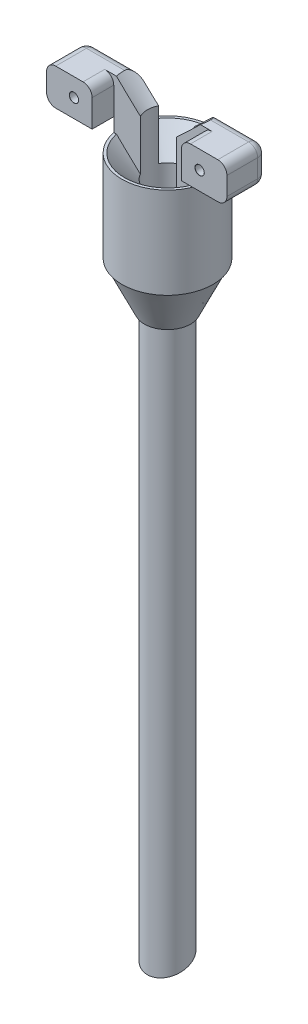
SolidWorks part; units mm, degrees
ref_plane "Front Plane" through (0, 0, 0) normal (0, 0, 1) x (1, 0, 0)
ref_plane "Top Plane" through (0, 0, 0) normal (0, 1, 0) x (1, 0, 0)
ref_plane "Right Plane" through (0, 0, 0) normal (1, 0, 0) x (0, 0, -1)
sketch "Sketch1" plane through (0, 0, 0) normal (0, 1, 0) x (1, 0, 0)
  circle A0 centre (0, 0) radius 1.7
  circle A1 centre (0, 0) radius 4.425
  dimension "D1" = 3.4
  dimension "D2" = 8.85
extrude "Boss-Extrude1" add sketch "Sketch1" along normal blind 130
chamfer "Chamfer1" distance 5 angle 60 1 edges at (0, 130, 1.7) first distance on face at (0, 130, 4.425)
ref_plane "Plane1" through (0, 126.0596, 0) normal (0, 1, 0) x (1, 0, 0)
sketch "Sketch2" plane through (0, 126.0596, 0) normal (0, 1, 0) x (1, 0, 0)
  circle A0 centre (0, 0) radius 10
  circle A1 centre (0, 0) radius 4.425
  dimension "D1" = 20
extrude "Boss-Extrude2" add sketch "Sketch2" along normal blind 20 separate body
ref_point "Point1"
ref_axis "Axis1" through (0, 126.0596, 0) along (0, -1, 0)
sketch "Sketch5" plane through (0, 126.0596, 0) normal (0, -1, 0) x (1, 0, 0)
  line L0 (0, 0) -> (2.7, 3.5058)
  circle A0 centre (0, 0) radius 4.425 construction
ref_plane "Plane2" through (2.7, 126.0596, 3.5058) normal (0.6102, 0, 0.7923) x (0.7923, 0, -0.6102)
sketch "Sketch10" plane through (0, 146.0596, 0) normal (0, 1, 0) x (1, 0, 0)
  line L0 (-3.9472, -2) -> (-9.798, -2)
  line L1 (-3.9472, 2) -> (-9.798, 2)
  line L2 (3.9472, 2) -> (9.798, 2)
  line L3 (3.9472, -2) -> (9.798, -2)
  line L4 (9.798, 2) -> (9.798, -2)
  line L5 (-9.798, 2) -> (-9.798, -2)
  line L6 (0, 10) -> (0, -10) construction
  circle A0 centre (0, 0) radius 4.425 construction
  circle A1 centre (0, 0) radius 10 construction
  circle A2 centre (0, 0) radius 4.425 construction
  arc A4 (3.9472, 2) -> (3.9472, -2) centre (0, 0) cw
  arc A5 (-3.9472, -2) -> (-3.9472, 2) centre (0, 0) cw
  dimension "D1" = 4
extrude "Boss-Extrude5" add sketch "Sketch10" along normal blind 11
sketch "Sketch11" plane through (9.798, 0, 0) normal (1, 0, 0) x (0, 0, -1)
  line L0 (-2, 146.0596) -> (2, 146.0596) construction
  line L1 (-2, 157.0596) -> (2, 157.0596)
  line L2 (-2, 157.0596) -> (-2, 149.0596)
  line L3 (-2, 149.0596) -> (2, 149.0596)
  line L4 (2, 157.0596) -> (2, 149.0596)
  line L5 (2, 157.0596) -> (2, 146.0596) construction
  dimension "D1" = 3
extrude "Boss-Extrude6" add sketch "Sketch11" along normal blind 10
sketch "Sketch13" plane through (0, 0, 2) normal (0, 0, 1) x (1, 0, 0)
  line L1 (9.798, 149.0596) -> (19.798, 149.0596)
  line L2 (9.798, 149.0596) -> (9.798, 157.0596)
  line L3 (9.798, 157.0596) -> (19.798, 157.0596)
  line L4 (19.798, 149.0596) -> (19.798, 157.0596)
extrude "Boss-Extrude7" add sketch "Sketch13" along normal blind 4.75
fillet "Fillet1" radius 2 3 edges at (9.798, 157.0596, 4.375) (19.798, 149.0596, 2.375) (19.798, 157.0596, 2.375)
ref_plane "Plane3" through (0, 0, 0) normal (1, 0, 0) x (0, 0, -1)
mirror "Mirror1" about plane through (0, 0, 0) normal (1, 0, 0) of "Fillet1", "Boss-Extrude6", "Boss-Extrude5", "Boss-Extrude7"
chamfer "Chamfer4" distance 5 angle 45 2 edges at (-4.425, 157.0596, 0) (4.425, 157.0596, 0)
chamfer "Chamfer2" distance 5 angle 45 2 edges at (0, 146.0596, 4.425) (0, 146.0596, -4.425)
sketch "Sketch7" plane through (0, 126.0596, 0) normal (0, -1, 0) x (1, 0, 0)
  circle A0 centre (0, 0) radius 4.425
  circle A1 centre (0, 0) radius 9.75
extrude "Boss-Extrude3" add sketch "Sketch7" along normal blind 10
chamfer "Chamfer3" distance 10 angle 25 1 edges at (0, 116.0596, -9.75) first distance on face at (0, 116.0596, -9.75)
sketch "Sketch8" plane through (0, 0, 0) normal (0, -1, 0) x (1, 0, 0)
  circle A0 centre (0, 0) radius 1.7
  circle A1 centre (0, 0) radius 4.425
  circle A4 centre (0, 0) radius 1.7 construction
  circle A5 centre (0, 0) radius 4.425 construction
extrude "Boss-Extrude4" add sketch "Sketch8" along normal blind 8
sketch "Sketch9" plane through (0, 0, 0) normal (1, 0, 0) x (0, 0, -1)
  line L0 (-4.425, -8) -> (4.425, -5)
  line L1 (4.425, -8) -> (4.425, 116.0596) construction
  line L2 (4.425, -5) -> (4.425, -8)
  line L3 (4.425, -8) -> (-4.425, -8)
  dimension "D1" = 3
extrude "Cut-Extrude1" cut sketch "Sketch9" against normal blind 8 and the other way blind 8
fillet "Fillet2" radius 2 10 edges at (13.798, 149.0596, -2) (19.2122, 149.6454, -2) (19.798, 153.0596, -2) (19.2122, 156.4738, -2) (-13.798, 149.0596, -2) (-19.2122, 149.6454, -2) (-19.798, 153.0596, -2) (-19.2122, 156.4738, -2) (13.5042, 157.0596, -2) (-13.5042, 157.0596, -2)
sketch "Sketch14" plane through (0, 0, 6.75) normal (0, 0, 1) x (1, 0, 0)
  line L0 (9.798, 149.0596) -> (17.798, 149.0596) construction
  line L1 (19.4941, 149.0596) -> (14.3598, 149.0596)
  line L2 (19.4941, 149.0596) -> (19.4941, 154.0596)
  line L3 (19.4941, 154.0596) -> (14.3598, 154.0596)
  line L4 (14.3598, 149.0596) -> (14.3598, 154.0596)
  dimension "D1" = 5
hole_wizard "Ø2.0mm Dowel Hole1" positions "Sketch16" profile "Sketch17" hole size "Ø2.0" standard "ANSI Metric" end condition up to next
sketch "Sketch16" plane through (0, 0, -2) normal (0, 0, -1) x (-1, 0, 0)
  line L0 (-17.798, 153.0596) -> (17.798, 153.0596) construction
  line L1 (-17.798, 155.0596) -> (-17.798, 151.0596) construction
  line L2 (17.798, 151.0596) -> (17.798, 155.0596) construction
  point P0 (13.798, 153.0596)
  point P2 (-13.798, 153.0596)
  dimension "D1" = 4
  dimension "D2" = 4
sketch "Sketch17" plane through (-13.798, 153.0596, -2) normal (1, 0, 0) x (0, 1, 0)
  line L0 (0, 0) -> (0, 8.75)
  line L1 (0, 8.75) -> (1.025, 8.75)
  line L2 (1, 8.725) -> (1, 0.025)
  line L3 (1, 0.025) -> (1.025, 0)
  line L5 (1.025, 0) -> (0, 0)
  line L6 (-1, 0.025) -> (-1.025, 0) construction
  line L7 (1.025, 8.75) -> (1, 8.725)
  line L8 (-1.025, 8.75) -> (-1, 8.725) construction
  line L11 (0, -6.35) -> (0, 107.95) construction
  dimension "Thru Hole Dia." = 2
  dimension "Thru Hole Depth" = 8.75
  dimension "Near C'Sink Dia." = 2.05
  dimension "Near C'Sink Angle" = 90
  dimension "Far C'Sink Dia." = 2.05
  dimension "Far C'Sink Angle" = 90
equation "\"D2@Sketch16\"=\"D1@Sketch16\""
